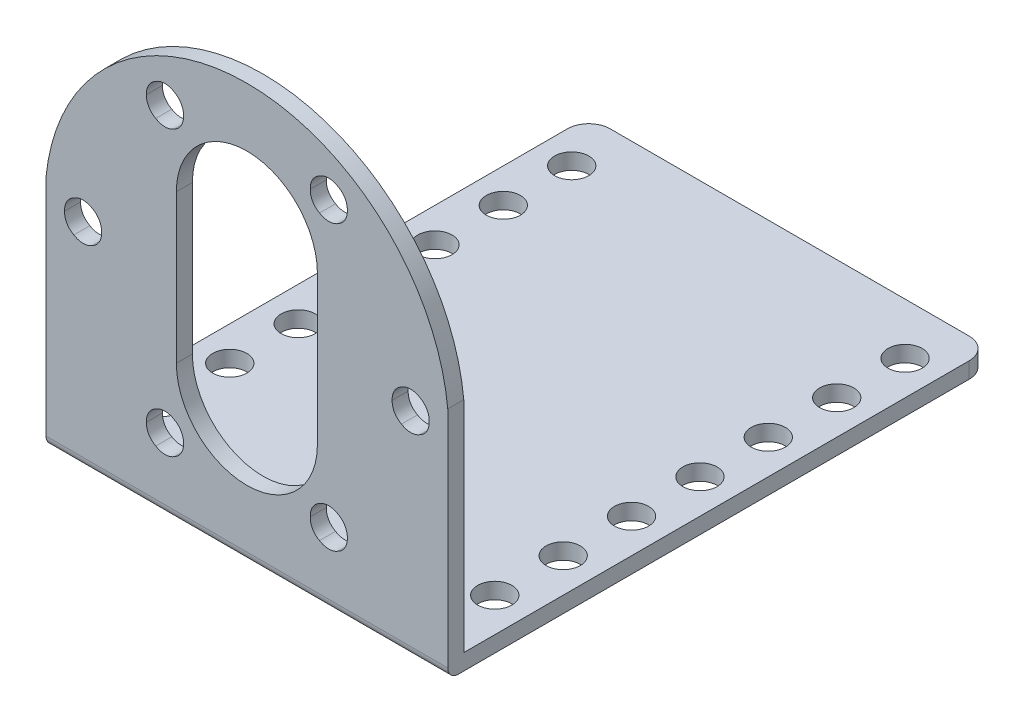
SolidWorks part; units mm, degrees
ref_plane "Front Plane" through (0, 0, 0) normal (0, 0, 1) x (1, 0, 0)
ref_plane "Top Plane" through (0, 0, 0) normal (0, 1, 0) x (1, 0, 0)
ref_plane "Right Plane" through (0, 0, 0) normal (1, 0, 0) x (0, 0, -1)
sketch "Sketch1" plane through (0, 0, 0) normal (0, 0, 1) x (1, 0, 0)
  line L0 (0, 0) -> (0, 39) construction
  line L1 (-18.8, 0) -> (18.8, 0)
  line L2 (-18.8, 0) -> (-18.8, 22)
  line L4 (18.8, 0) -> (18.8, 22)
  line L6 (-6.6, 12.9994) -> (-6.6, 26.8994)
  line L8 (6.6, 12.9994) -> (6.6, 26.8994)
  arc A0 (-18.8, 22) -> (18.8, 22) centre (0, 20.1047) cw
  arc A1 (-6.6, 26.8994) -> (6.6, 26.8994) centre (0, 26.9) cw
  arc A2 (-6.6, 12.9994) -> (6.6, 12.9994) centre (0, 13) ccw
  dimension "D3" = 39
  dimension "D5" = 27.1
  dimension "D6" = 5.5
  dimension "D1" = 37.6
  dimension "D2" = 22
  dimension "D4" = 13.2
  dimension "D7" = 13.9
extrude "Boss-Extrude1" add sketch "Sketch1" along normal blind 1.5
sketch "Sketch2" plane through (0, 0, 0) normal (0, -1, 0) x (1, 0, 0)
  line L0 (18.8, 1.5) -> (18.8, 0) construction
  line L1 (-18.8, 1.5) -> (18.8, 1.5)
  line L2 (-18.8, 1.5) -> (-18.8, -49.3)
  line L3 (-18.8, -49.3) -> (18.8, -49.3)
  line L4 (18.8, 1.5) -> (18.8, -49.3)
  dimension "D1" = 50.8
extrude "Boss-Extrude2" add sketch "Sketch2" against normal blind 1.5
fillet "Fillet1" radius 1 1 edges at (0, 0, 1.5)
fillet "Fillet2" radius 2 2 edges at (-18.8, 0.75, -49.3) (18.8, 0.75, -49.3)
sketch "Sketch3" plane through (0, 0, 0) normal (0, -1, 0) x (1, 0, 0)
  line L0 (-16.8, -49.3) -> (16.8, -49.3) construction
  line L1 (-18.8, 0.5) -> (-18.8, -47.3) construction
  circle A0 centre (-15.6, -44.5) radius 1.6
  dimension "D1" = 3.2
  dimension "D2" = 4.8
  dimension "D3" = 3.2
extrude "Cut-Extrude1" cut sketch "Sketch3" against normal up to next
pattern_linear "LPattern1" count 7 spacing 6.4 along (0, 0, 1) of "Cut-Extrude1"
mirror "Mirror1" about plane through (0, 0, 0) normal (1, 0, 0) of "LPattern1", "Cut-Extrude1"
sketch "Sketch4" plane through (0, 0, 1.5) normal (0, 0, 1) x (1, 0, 0)
  line L0 (0, 0) -> (0, 39) construction
  line L1 (-7.6648, 33.2258) -> (-5.815, 30.0218) construction
  line L2 (-5.815, 30.0218) -> (0, 19.95) construction
  line L3 (0, 19.95) -> (-5.815, 9.8782) construction
  line L4 (0, 19.95) -> (5.815, 9.8782) construction
  line L5 (5.815, 9.8782) -> (7.6648, 6.6742) construction
  line L6 (0, 19.95) -> (5.815, 30.0218) construction
  line L7 (5.815, 30.0218) -> (7.6648, 33.2258) construction
  line L8 (-5.815, 9.8782) -> (-7.6648, 6.6742) construction
  line L9 (7.325, 33.2258) -> (7.6648, 33.2258) construction
  line L10 (7.6648, 33.2258) -> (9.5146, 36.4297) construction
  circle A0 centre (7.6648, 33.2258) radius 1.6
  arc A1 (18.8, 22) -> (-18.8, 22) centre (0, 20.1047) ccw construction
  circle A3 centre (15.3295, 19.95) radius 1.6
  circle A4 centre (7.6648, 6.6742) radius 1.6
  circle A5 centre (-7.6648, 6.6742) radius 1.6
  circle A6 centre (-15.3295, 19.95) radius 1.6
  circle A7 centre (-7.6648, 33.2258) radius 1.6
  arc A8 (-6.6, 12.9994) -> (6.6, 12.9994) centre (0, 13) ccw construction
  arc A9 (6.6, 26.8994) -> (-6.6, 26.8994) centre (0, 26.9) ccw construction
  point P26 (0, 19.95)
  dimension "D1" = 3.2
  dimension "D2" = 6
extrude "Cut-Extrude2" cut sketch "Sketch4" against normal up to next
pattern_circular "CirPattern1" count 6 over 360 about axis through (0, 20.1047, 1.5) along (0, 0, -1) of "Cut-Extrude2"
